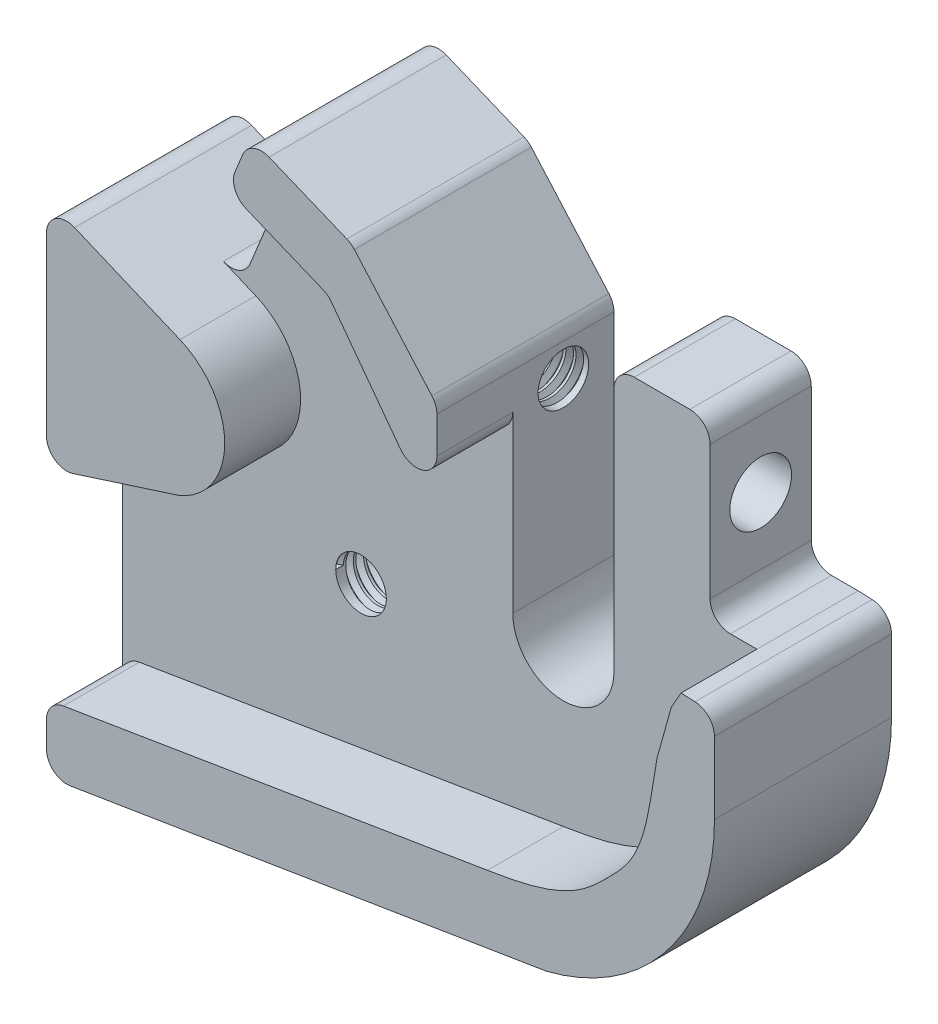
SolidWorks part; units mm, degrees
note: The reader was unsure of these and kept them because the rebuilt part matched: shared geometry of "Sketch1<7>".
ref_plane "Front Plane" through (0, 0, 0) normal (0, 0, 1) x (1, 0, 0)
ref_plane "Top Plane" through (0, 0, 0) normal (0, 1, 0) x (1, 0, 0)
ref_plane "Right Plane" through (0, 0, 0) normal (1, 0, 0) x (0, 0, -1)
sketch "Sketch1" plane through (0, 0, 0) normal (0, 0, 1) x (1, 0, 0)
  line L0 (-48.8998, -64.1664) -> (-34.4801, 53.9567) construction
  line L3 (0, 51.4823) -> (78.4652, 51.4823)
  line L4 (78.4652, 0) -> (78.4652, 51.4823)
  line L5 (-0.9054, 14.8469) -> (9.0946, 14.8469)
  line L6 (9.0946, 14.8469) -> (9.0946, -2.1531)
  line L7 (9.0946, -2.1531) -> (-0.9054, -2.1531)
  line L8 (-0.9054, -2.1531) -> (-0.9054, 14.8469)
  line L9 (-11.6542, 28.4583) -> (-0.9054, 14.02)
  line L10 (-52.5896, 45.2866) -> (-11.6542, 28.4583)
  line L11 (9.0946, 14.8469) -> (9.0946, 29.052)
  line L12 (9.0946, 29.052) -> (18.5946, 29.052)
  line L13 (-61.5112, 32.1478) -> (-26.3036, 17.3197)
  line L14 (-26.3036, 17.3197) -> (-29.1124, 10.6505)
  line L15 (-29.1124, 10.6505) -> (-31.9213, 3.9813)
  line L16 (-70.304, -10.1797) -> (-26.4323, 3.9286)
  line L17 (-39.4934, 22.8747) -> (-39.4934, -0.2716)
  line L18 (-26.4323, 3.9286) -> (-29.1124, 10.6505)
  line L19 (-29.1124, 10.6505) -> (-31.7926, 17.3724)
  line L20 (4.0946, -12.9031) -> (-39.4934, -20.0716)
  line L21 (4.0946, -2.1531) -> (19.0946, -2.1531) construction
  line L22 (23.2246, 11.8381) -> (22.2572, 10.123)
  line L23 (23.2246, 11.8381) -> (34.7443, 11.3546)
  line L24 (-0.9054, 14.8469) -> (-0.9054, 20.5391)
  line L25 (-19.3381, 38.1043) -> (-8.9222, 33.8224)
  line L26 (-11.6542, 28.4583) -> (-9.3728, 34.0076)
  line L27 (-7.3088, 22.6214) -> (-2.496, 26.2043)
  line L28 (-2.496, 26.2043) -> (-9.3728, 34.0076)
  line L29 (-70.5009, -25.054) -> (-69.6167, -30.4821)
  line L31 (26.529, 2.6512) -> (26.529, -15.9236)
  line L32 (27.019, 6.583) -> (34.7443, 6.583)
  line L33 (34.7443, 6.583) -> (34.7443, 11.3546)
  line L34 (-11.6542, 28.4583) -> (-8.9222, 28.4583)
  line L35 (-70.5009, -25.054) -> (-70.304, -10.1797)
  line L36 (18.5946, 29.052) -> (18.5946, 11.8381)
  line L37 (-39.4934, -0.2716) -> (-39.4934, -26.678)
  line L38 (-39.4934, 22.8747) -> (-39.4934, 39.9028)
  line L39 (22.2572, 10.123) -> (21.4546, 7.2463)
  line L40 (21.4546, 7.2463) -> (20.8501, 5.08)
  line L41 (20.8501, 5.08) -> (20.5233, 3.0772)
  line L42 (-8.9222, 28.4583) -> (-8.9222, 25.2921)
  line L43 (-19.3381, 38.1043) -> (-21.6194, 32.5549)
  line L44 (-0.9054, 20.5391) -> (-0.9054, 24.0677)
  line L45 (-2.496, 26.2043) -> (-0.9054, 24.3993)
  line L46 (-21.6194, 32.5549) -> (-27.6495, 17.8865)
  line L47 (-39.4934, -26.678) -> (29.4812, -15.4427)
  line L48 (4.5907, 2.6512) -> (19.4637, 2.6512) construction
  line L49 (19.4637, 2.6512) -> (26.529, 2.6512) construction
  line L50 (26.529, 2.6512) -> (26.529, 6.583)
  line L51 (26.529, 6.583) -> (27.019, 6.583)
  line L52 (-0.9054, 24.3993) -> (-0.9054, 24.0677)
  line L53 (18.5946, 11.8381) -> (23.2246, 11.8381)
  line L54 (4.0946, -2.1531) -> (-15.9054, -2.1531)
  line L55 (26.529, 6.583) -> (26.529, 11.6994)
  line L56 (4.0946, -2.1531) -> (4.0946, -12.9031) construction
  circle A0 centre (4.0946, 2.8469) radius 5
  circle A1 centre (4.0946, 9.8469) radius 5
  circle A2 centre (-29.1124, 10.6505) radius 7.2365
  circle A4 centre (4.5907, 2.6512) radius 21.9383
  circle A5 centre (-15.9054, -2.1531) radius 3
  spline S0 degree 3 poles (4.0946, -12.9031) (7.1977, -12.407) (12.0844, -11.481) (15.9679, -7.6449) (18.0516, -5.4431) (19.7772, -1.9974) (20.1723, 1.0102) (20.5233, 3.0772) knots 0 0 0 0 0.38814 0.547132 0.64369 0.748457 1 1 1 1
  dimension "D4" = 9.5
  dimension "D7" = 6
  dimension "D1" = 119
  dimension "D2" = 10
  dimension "D3" = 17
  dimension "D5" = 18
  dimension "D6" = 6
  dimension "D8" = 19.8
  dimension "D9" = 15
  dimension "D10" = 10.75
extrude "Boss-Extrude2" add sketch "Sketch1" along normal blind 10
extrude "Boss-Extrude3" add sketch "Sketch1<7>" along normal blind 17.5
sketch "Sketch1<7>" plane through (0, 0, 0) normal (0, 0, 1) x (1, 0, 0) same geometry as "Sketch1"
sketch "Sketch2" plane through (18.5946, 0, 0) normal (1, 0, 0) x (0, 0, -1)
  line L0 (-5, 29.052) -> (-5, 20.445) construction
  line L1 (-10, 29.052) -> (0, 29.052) construction
  line L2 (-10, 20.445) -> (-5, 20.445) construction
  line L3 (-10, 29.052) -> (-10, 11.8381) construction
  circle A0 centre (-5, 20.445) radius 3.05
  dimension "D1" = 6.1
hole_wizard "Tap Drill for M6x1.0 Tap3" positions "3DSketch3" profile "Sketch7" hole size "M6x1.0" standard "ANSI Metric"
sketch3d "3DSketch3"
  point P0 (18.5946, 20.445, 5)
sketch "Sketch7" plane through (18.5946, 20.445, 5) normal (0, 1, 0) x (0, 0, -1)
  line L0 (0, 0) -> (0, 44.5022)
  line L1 (0, 44.5022) -> (2.5, 43)
  line L2 (2.5, 43) -> (2.5, 0)
  line L5 (2.5, 0) -> (0, 0)
  line L10 (0, 44.5022) -> (-2.5, 43) construction
  line L11 (0, -6.35) -> (0, 107.95) construction
  dimension "Hole Dia." = 5
  dimension "Hole Depth" = 43
  dimension "Drill Angle" = 118
fillet "Fillet1" radius 2 15 edges at (-39.4934, -0.2716, 13.75) (-39.4934, -26.678, 8.75) (-0.9054, 14.02, 13.75) (-21.6194, 32.5549, 13.75) (-19.3381, 38.1043, 8.75) (-39.4934, 22.8747, 8.75) (-27.6495, 17.8865, 5) (-9.3728, 34.0076, 8.75) (9.0946, 29.052, 5) (18.5946, 29.052, 5) (18.5946, 11.8381, 5) (-0.9054, 24.3993, 8.75) (-11.6542, 28.4583, 13.75) (26.529, 11.6994, 8.75) (-39.4934, -20.0716, 13.75)
hole_wizard "Tap Drill for M6x1.0 Tap2" positions "3DSketch2" profile "Sketch5" hole size "M6x1.0" standard "ANSI Metric" end condition through all
sketch3d "3DSketch2"
  line L0 (4.0946, -2.1531, 10) -> (-15.9054, -2.1531, 10)
  arc A0 (-0.9054, 2.8469, 10) -> (9.0946, 2.8469, 10) centre (4.0946, 2.8469, 10) ccw construction
  point P0 (-15.9054, -2.1531, 10)
  point P8 (4.0946, 2.8469, 15)
  dimension "D1" = 20
sketch "Sketch5" plane through (-15.9054, -2.1531, 10) normal (1, 0, 0) x (0, -1, 0)
  line L0 (0, 0) -> (0, 10)
  line L1 (0, 10) -> (2.5, 10)
  line L2 (2.5, 10) -> (2.5, 0)
  line L5 (2.5, 0) -> (0, 0)
  line L11 (0, -6.35) -> (0, 107.95) construction
  dimension "Thru Hole Dia." = 5
  dimension "Thru Hole Depth" = 10
thread "Thread1" pitch 1 start angle 0, offset 0, length 23, pitch 1, diameter 5
ref_plane "Plane2" through (-0.9054, 20.445, 7.5) normal (0, -1, 0) x (0, 0, 1)
sketch "Thread Profile2" plane through (-0.9054, 20.445, 7.5) normal (0, -1, 0) x (0, 0, 1)
  line L0 (0, 0) -> (0, 1) construction
  line L1 (0, 0) -> (0.5413, 0.3125)
  line L2 (0.5413, 0.3125) -> (0.5413, 0.4375)
  line L3 (0.5413, 0.4375) -> (0, 0.75)
  line L4 (0.5413, 0.375) -> (0, 0.375) construction
  line L11 (0, 0) -> (0, 0.75)
  point P2 (0, 0)
  dimension "Pitch" = 1
  dimension "Profile_Angle" = 60
  dimension "Profile_Land" = 0.125
  dimension "Profile_Height" = 0.5413
extrude "Cut-Extrude2" cut sketch "Sketch2" against normal blind 10 contours A0
thread "Thread2" pitch 1 profile "Thread Profile3" start angle 0, offset 0, length 13, pitch 1, diameter 5
ref_plane "Plane3" through (-18.4054, -2.1531, 10) normal (0, -1, 0) x (-1, 0, 0)
sketch "Thread Profile3" plane through (-18.4054, -2.1531, 10) normal (0, -1, 0) x (-1, 0, 0)
  line L0 (0, 0) -> (0, 1) construction
  line L1 (0, 0) -> (0.5413, 0.3125)
  line L2 (0.5413, 0.3125) -> (0.5413, 0.4375)
  line L3 (0.5413, 0.4375) -> (0, 0.75)
  line L4 (0.5413, 0.375) -> (0, 0.375) construction
  line L11 (0, 0) -> (0, 0.75)
  point P2 (0, 0)
  dimension "Pitch" = 1
  dimension "Profile_Angle" = 60
  dimension "Profile_Land" = 0.125
  dimension "Profile_Height" = 0.5413
